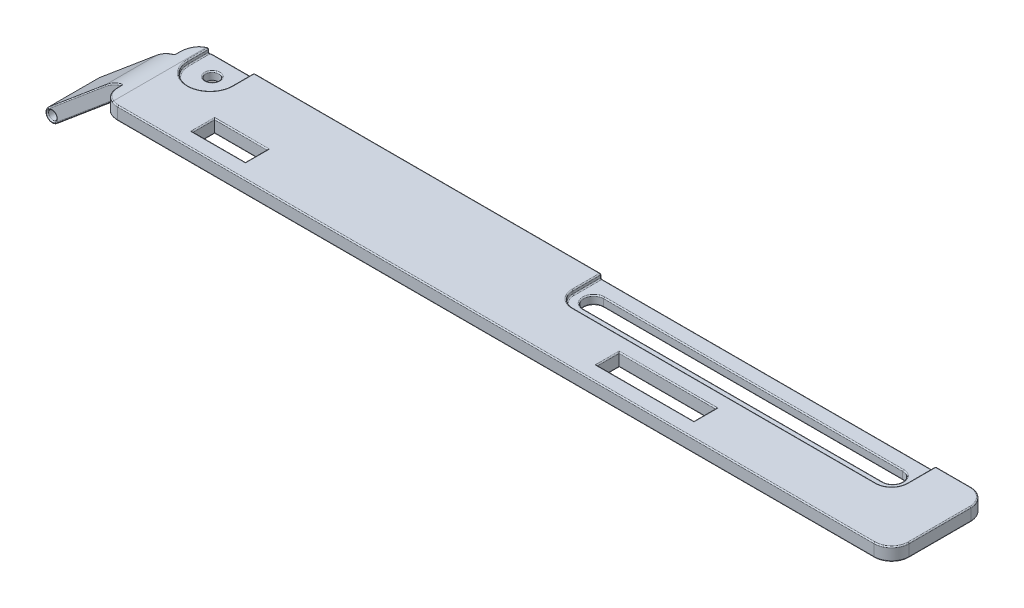
SolidWorks part; units mm, degrees
ref_plane "Front Plane" through (0, 0, 0) normal (0, 0, 1) x (1, 0, 0)
ref_plane "Top Plane" through (0, 0, 0) normal (0, 1, 0) x (1, 0, 0)
ref_plane "Right Plane" through (0, 0, 0) normal (1, 0, 0) x (0, 0, -1)
sketch "Sketch1" plane through (0, 0, 0) normal (0, 0, 1) x (1, 0, 0)
  line L0 (-182.7882, -2.3396) -> (-195, -12.5865)
  line L1 (0, 0) -> (-176.3603, 0)
  line L2 (0, 0) -> (0, 3)
  line L3 (0, 3) -> (-177.4522, 3)
  line L6 (-196.9284, -10.2884) -> (-183.8801, 0.6604)
  arc A0 (-196.9284, -10.2884) -> (-195, -12.5865) centre (-195.9642, -11.4374) ccw
  circle A1 centre (-195.9642, -11.4374) radius 1
  arc A2 (-176.3603, 0) -> (-182.7882, -2.3396) centre (-176.3603, -10) ccw
  arc A3 (-177.4522, 3) -> (-183.8801, 0.6604) centre (-177.4522, -7) ccw
  point P11 (-180, 0)
  dimension "D1" = 2
  dimension "D2" = 10
  dimension "D6" = 10
  dimension "D3" = 140
  dimension "D4" = 15
  dimension "D5" = 3
extrude "Boss-Extrude1" add sketch "Sketch1" along normal blind 11 and the other way blind 11
sketch "Sketch2" plane through (0, 0, 11) normal (0, 0, 1) x (1, 0, 0)
  line L0 (0, 0) -> (0, 3) construction
  line L1 (-210.1499, 9.6657) -> (-180, 9.6657)
  line L2 (-210.1499, 9.6657) -> (-210.1499, -17.5852)
  line L3 (-210.1499, -17.5852) -> (-180, -17.5852)
  line L4 (-180, 9.6657) -> (-180, -17.5852)
  dimension "D1" = 180
extrude "Cut-Extrude1" cut sketch "Sketch2" against normal blind 5
sketch "Sketch3" plane through (0, 0, -11) normal (0, 0, -1) x (-1, 0, 0)
  line L0 (0, 0) -> (0, 3) construction
  line L1 (180, 28.7292) -> (251.8205, 28.7292)
  line L2 (180, 28.7292) -> (180, -54.8714)
  line L3 (180, -54.8714) -> (251.8205, -54.8714)
  line L4 (251.8205, 28.7292) -> (251.8205, -54.8714)
  dimension "D1" = 180
extrude "Cut-Extrude2" cut sketch "Sketch3" against normal blind 5
sketch "Sketch4" plane through (0, 3, 0) normal (0, 1, 0) x (1, 0, 0)
  line L0 (0, -11) -> (-177.4522, -11) construction
  line L1 (-162.4522, -2.5) -> (-150.4522, -2.5)
  line L2 (-162.4522, -2.5) -> (-162.4522, -7.5)
  line L3 (-162.4522, -7.5) -> (-150.4522, -7.5)
  line L4 (-150.4522, -2.5) -> (-150.4522, -7.5)
  line L5 (-70.4522, -2.5) -> (-48.4522, -2.5)
  line L6 (-70.4522, -2.5) -> (-70.4522, -7.5)
  line L7 (-70.4522, -7.5) -> (-48.4522, -7.5)
  line L8 (-48.4522, -2.5) -> (-48.4522, -7.5)
  line L9 (-177.4522, 11) -> (-177.4522, -11) construction
  dimension "D1" = 5
  dimension "D2" = 12
  dimension "D3" = 3.5
  dimension "D4" = 15
  dimension "D5" = 3.5
  dimension "D6" = 80
  dimension "D7" = 22
  dimension "D8" = 5
extrude "Cut-Extrude3" cut sketch "Sketch4" against normal up to next
sketch "Sketch5" plane through (0, 3, 0) normal (0, 1, 0) x (1, 0, 0)
  line L0 (0, 11) -> (-177.4522, 11) construction
  line L1 (-88, 11) -> (-12, 11)
  line L2 (-88, 11) -> (-88, 4.5)
  line L3 (-84.5, 1) -> (-15.5, 1)
  line L4 (-12, 11) -> (-12, 4.5)
  line L5 (0, 11) -> (0, -11) construction
  line L10 (-180, 6) -> (-180, 11) construction
  line L11 (-177, 6) -> (-177, 11)
  line L12 (-177, 11) -> (-167, 11)
  line L13 (-167, 11) -> (-167, 6)
  arc A0 (-15.5, 1) -> (-12, 4.5) centre (-15.5, 4.5) ccw
  arc A1 (-84.5, 1) -> (-88, 4.5) centre (-84.5, 4.5) cw
  arc A2 (-177, 6) -> (-167, 6) centre (-172, 6) ccw
  point P14 (-12, 1)
  point P17 (-88, 1)
  dimension "D4" = 3.5
  dimension "D5" = 10
  dimension "D1" = 76
  dimension "D2" = 12
  dimension "D3" = 10
  dimension "D6" = 5
  dimension "D7" = 8
extrude "Cut-Extrude4" cut sketch "Sketch5" against normal blind 1
sketch "Sketch6" plane through (0, 3, 0) normal (0, 1, 0) x (1, 0, 0)
  line L1 (-84, 7.5) -> (-16, 7.5)
  line L3 (-84, 3) -> (-16, 3)
  line L6 (-12, 11) -> (-88, 11) construction
  line L7 (-12, 4.5) -> (-12, 11) construction
  line L8 (-177, 11) -> (-177, 6) construction
  arc A0 (-84, 7.5) -> (-84, 3) centre (-84, 5.25) ccw
  arc A1 (-16, 3) -> (-16, 7.5) centre (-16, 5.25) ccw
  circle A2 centre (-172, 6.5) radius 1.5
  arc A3 (-177, 6) -> (-167, 6) centre (-172, 6) ccw construction
  point P15 (-172, 1)
  dimension "D5" = 3
  dimension "D1" = 4.5
  dimension "D2" = 68
  dimension "D3" = 4
  dimension "D4" = 3.5
  dimension "D6" = 5.5
  dimension "D7" = 5
extrude "Cut-Extrude5" cut sketch "Sketch6" against normal up to next
fillet "Fillet1" radius 4 4 edges at (-180, 0.992, 11) (-180, 0.992, -11) (0, 1.5, 11) (0, 1.5, -11)
fillet "Fillet2" radius 0.25 86 edges at (-167, 2.5, -11) (-177, 2.5, -10.873) (-12, 2.5, -11) (-88, 2.5, -11) (-180, -0.6859, 6.5) (-178.6841, -0.2738, 9.9657) (-180, -0.6859, -6.5) (-179.1965, -0.4106, -9.4047) (-180, 2.67, -6.5) (-179.4342, 2.8016, -9.0509) (-180, 2.67, 6.5) (-179.1546, 2.854, 9.4593) (-167, 2, -8.5) (-172, 2, -1) (-177, 2, -8.4365) (-176.504, 2, -10.9681) (-171.5, 2, -11) (-173.5, 2, -6.5) (-196.9642, -11.4374, -6) (-181.4615, -1.399, -6) (-180, 0.992, -6) (-182.0511, 1.8797, -6) (-190.4042, -4.814, -6) (-197.1132, -12.4016, -6) (-188.8941, -7.463, -6) (-194.9642, -11.4374, 6) (-181.4615, -1.399, 6) (-188.8941, -7.463, 6) (-197.1132, -12.4016, 6) (-190.4042, -4.814, 6) (-182.0511, 1.8797, 6) (-180, 0.992, 6) (-1.1716, 0, 9.8284) (0, 0, 0) (-1.1716, 0, -9.8284) (-90, 0, -11) (-176.1803, 0, -10.9959) (-176.1803, 0, 10.9959) (-90, 0, 11) (-59.4522, 0, 2.5) (-48.4522, 0, 5) (-59.4522, 0, 7.5) (-70.4522, 0, 5) (-156.4522, 0, 2.5) (-150.4522, 0, 5) (-156.4522, 0, 7.5) (-162.4522, 0, 5) (-172, 0, -8) (-50, 0, -7.5) (-13.75, 0, -5.25) (-50, 0, -3) (-86.25, 0, -5.25) (-50, 2, -11) (-12, 2, -7.75) (-13.0251, 2, -2.0251) (-50, 2, -1) (-86.9749, 2, -2.0251) (-88, 2, -7.75) (-13.75, 2, -5.25) (-50, 2, -7.5) (-86.25, 2, -5.25) (-50, 2, -3) (-59.4522, 3, 7.5) (-48.4522, 3, 5) (-59.4522, 3, 2.5) (-70.4522, 3, 5) (-156.4522, 3, 7.5) (-150.4522, 3, 5) (-156.4522, 3, 2.5) (-162.4522, 3, 5) (-177.2283, 3, -10.8068) (-177, 3, -8.4365) (-172, 3, -1) (-167, 3, -8.5) (-127.5, 3, -11) (-88, 3, -7.75) (-86.9749, 3, -2.0251) (-50, 3, -1) (-13.0251, 3, -2.0251) (-12, 3, -7.75) (-8, 3, -11) (-1.1716, 3, -9.8284) (0, 3, 0) (-1.1716, 3, 9.8284) (-90, 3, 11) (-176.7388, 3, 10.9312)
